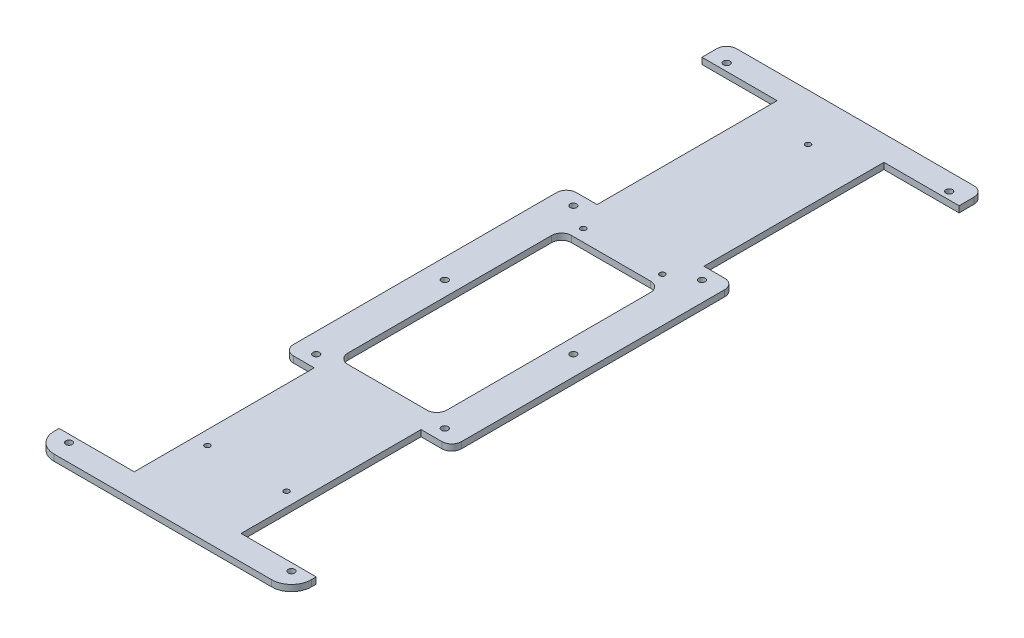
SolidWorks part; units mm, degrees
ref_plane "Front Plane" through (0, 0, 0) normal (0, 0, 1) x (1, 0, 0)
ref_plane "Top Plane" through (0, 0, 0) normal (0, 1, 0) x (1, 0, 0)
ref_plane "Right Plane" through (0, 0, 0) normal (1, 0, 0) x (0, 0, -1)
sketch "Sketch1" plane through (0, 0, 0) normal (0, 1, 0) x (1, 0, 0)
  line L0 (0, 0) -> (130, 0)
  line L1 (0, 0) -> (130, 0) construction
  line L2 (0, 0) -> (0, 350) construction
  line L3 (0, 350) -> (130, 350) construction
  line L4 (130, 0) -> (130, 350) construction
  line L5 (130, 0) -> (130, 12.5)
  line L6 (130, 12.5) -> (92, 12.5)
  line L7 (92, 12.5) -> (92, 103.5)
  line L11 (92, 246.5) -> (92, 337.5)
  line L12 (92, 337.5) -> (130, 337.5)
  line L13 (130, 337.5) -> (130, 350)
  line L14 (130, 350) -> (0, 350)
  line L15 (0, 350) -> (0, 337.5)
  line L16 (0, 337.5) -> (38, 337.5)
  line L17 (38, 337.5) -> (38, 246.5)
  line L21 (38, 103.5) -> (38, 12.5)
  line L22 (38, 12.5) -> (0, 12.5)
  line L23 (0, 12.5) -> (0, 0)
  line L24 (38, 246.5) -> (22.5, 246.5)
  line L25 (22.5, 246.5) -> (22.5, 103.5)
  line L26 (22.5, 103.5) -> (38, 103.5)
  line L27 (92, 246.5) -> (107.5, 246.5)
  line L28 (107.5, 246.5) -> (107.5, 103.5)
  line L29 (107.5, 103.5) -> (92, 103.5)
  dimension "D1" = 130
  dimension "D2" = 350
  dimension "D3" = 38
  dimension "D4" = 91
  dimension "D5" = 22.5
  dimension "D6" = 143
extrude "Boss-Extrude1" add sketch "Sketch1" along normal blind 3.175
fillet "Fillet1" radius 10 2 edges at (130, 1.5875, 0) (0, 1.5875, 0)
fillet "Fillet2" radius 5 6 edges at (0, 1.5875, -350) (130, 1.5875, -350) (107.5, 1.5875, -246.5) (107.5, 1.5875, -103.5) (22.5, 1.5875, -103.5) (22.5, 1.5875, -246.5)
sketch "Sketch2" plane through (0, 3.175, 0) normal (0, 1, 0) x (1, 0, 0)
  line L2 (32.5, 240) -> (32.5, 110) construction
  line L3 (22.5, 175) -> (32.5, 175) construction
  line L4 (22.5, 241.5) -> (22.5, 108.5) construction
  line L5 (65, 350) -> (65, 0) construction
  line L6 (125, 350) -> (5, 350) construction
  line L7 (10, 0) -> (120, 0) construction
  circle A0 centre (32.5, 240) radius 1.65
  circle A1 centre (32.5, 175) radius 1.65
  circle A2 centre (32.5, 110) radius 1.65
  circle A3 centre (97.5, 110) radius 1.65
  circle A4 centre (97.5, 175) radius 1.65
  circle A5 centre (97.5, 240) radius 1.65
  dimension "D3" = 3.3
  dimension "D1" = 10
  dimension "D2" = 130
extrude "Cut-Extrude1" cut sketch "Sketch2" against normal through all
sketch "Sketch3" plane through (0, 3.175, 0) normal (0, 1, 0) x (1, 0, 0)
  line L0 (0, 12.5) -> (8.75, 12.5) construction
  line L1 (38, 12.5) -> (0, 12.5) construction
  line L2 (8.75, 12.5) -> (8.75, 8.75) construction
  line L3 (65, 0) -> (65, 57.6288) construction
  line L4 (10, 0) -> (120, 0) construction
  circle A0 centre (8.75, 8.75) radius 1.65
  circle A1 centre (121.25, 8.75) radius 1.65
  dimension "D3" = 3.3
  dimension "D1" = 8.75
  dimension "D2" = 3.75
extrude "Cut-Extrude2" cut sketch "Sketch3" against normal through all
sketch "Sketch4" plane through (0, 3.175, 0) normal (0, 1, 0) x (1, 0, 0)
  line L0 (0, 337.5) -> (8.75, 337.5) construction
  line L1 (0, 337.5) -> (38, 337.5) construction
  line L2 (8.75, 337.5) -> (8.75, 341.25) construction
  line L3 (65, 350) -> (65, 288.2737) construction
  line L4 (125, 350) -> (5, 350) construction
  circle A0 centre (8.75, 341.25) radius 1.65
  circle A1 centre (121.25, 341.25) radius 1.65
  dimension "D3" = 3.3
  dimension "D1" = 8.75
  dimension "D2" = 3.75
extrude "Cut-Extrude3" cut sketch "Sketch4" against normal through all
sketch "Sketch5" plane through (0, 3.175, 0) normal (0, 1, 0) x (1, 0, 0)
  line L0 (38, 12.5) -> (92, 12.5) construction
  line L1 (65, 12.5) -> (65, 42.5) construction
  line L2 (45, 42.5) -> (85, 42.5) construction
  line L3 (65, 42.5) -> (65, 232.5) construction
  line L4 (45, 232.5) -> (85, 232.5) construction
  line L5 (65, 350) -> (65, 326.15) construction
  line L6 (125, 350) -> (5, 350) construction
  circle A0 centre (45, 42.5) radius 1.35
  circle A1 centre (85, 42.5) radius 1.35
  circle A2 centre (45, 232.5) radius 1.35
  circle A3 centre (85, 232.5) radius 1.35
  circle A4 centre (65, 326.15) radius 1.35
  point P8 (65, 42.5)
  point P14 (65, 232.5)
  dimension "D3" = 2.7
  dimension "D1" = 30
  dimension "D2" = 40
  dimension "D4" = 190
  dimension "D5" = 40
  dimension "D6" = 23.85
extrude "Cut-Extrude4" cut sketch "Sketch5" against normal blind 10
sketch "Sketch6" plane through (0, 3.175, 0) normal (0, 1, 0) x (1, 0, 0)
  line L0 (38, 246.5) -> (92, 246.5) construction
  line L1 (40, 226.5) -> (90, 226.5)
  line L2 (40, 226.5) -> (40, 113.5)
  line L3 (40, 113.5) -> (90, 113.5)
  line L4 (90, 226.5) -> (90, 113.5)
  line L5 (38, 103.5) -> (92, 103.5) construction
  line L6 (65, 246.5) -> (65, 103.5) construction
  point P13 (65, 113.5)
  point P16 (65, 103.5)
  dimension "D1" = 20
  dimension "D2" = 10
  dimension "D3" = 50
extrude "Cut-Extrude5" cut sketch "Sketch6" against normal blind 10
fillet "Fillet4" radius 5 4 edges at (90, 1.5875, -113.5) (40, 1.5875, -113.5) (90, 1.5875, -226.5) (40, 1.5875, -226.5)
